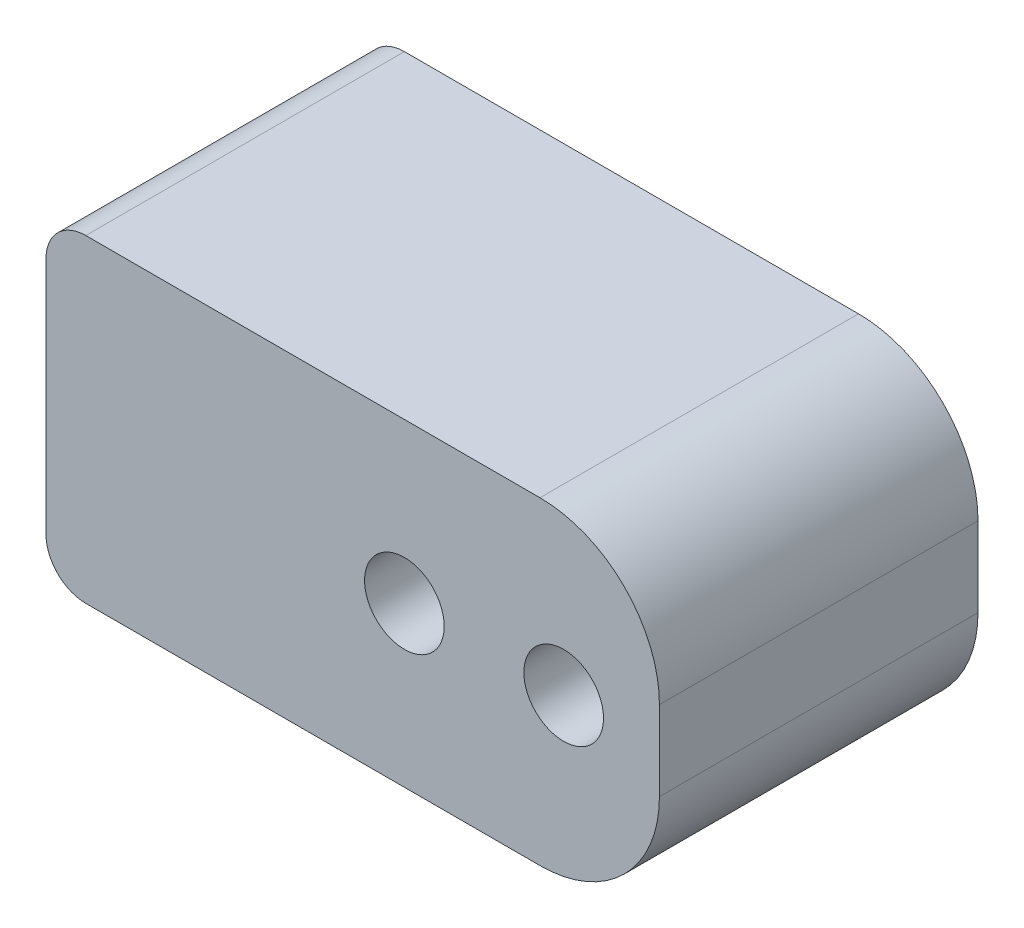
SolidWorks part; units mm, degrees
ref_plane "Front" through (0, 0, 0) normal (0, 0, 1) x (1, 0, 0)
ref_plane "Top" through (0, 0, 0) normal (0, 1, 0) x (1, 0, 0)
ref_plane "Right" through (0, 0, 0) normal (1, 0, 0) x (0, 0, -1)
sketch "Sketch1" plane through (0, 0, 0) normal (0, 0, 1) x (1, 0, 0)
  line L0 (-9, 4) -> (0, 4)
  line L1 (0, -4) -> (-9, -4)
  line L2 (-9, 4) -> (-9, -4)
  line L3 (55, 0) -> (-55, 0) construction
  line L4 (0, 4) -> (6.4045, 4)
  line L5 (0, 4) -> (0, -4)
  line L6 (0, -4) -> (6.4045, -4)
  line L7 (6.4045, 4) -> (6.4045, -4)
  circle A0 centre (0, 0) radius 4
  circle A1 centre (0, 0) radius 1
  circle A2 centre (4, 0) radius 1
  dimension "D1" = 8
  dimension "D3" = 2
  dimension "D4" = 4
  dimension "D2" = 9
extrude "Boss-Extrude1" add sketch "Sketch1" along normal blind 8 contours A0 L0 L2 L1 | A1 L5 A0 | A1 L5 A0 | A0 A2 L6 L7 L4 region at (-6.0028, 0, 0) region at (1.6632, 0, 0) region at (-1.7825, 0, 0) region at (3.2023, 3.8975, 0)
ref_plane "Plane1" through (0, 0, 4) normal (0, 0, 1) x (1, 0, 0)
sketch "Sketch3" plane through (0, 0, 4) normal (0, 0, 1) x (1, 0, 0)
  line L0 (4.4, 0) -> (-4.4, 0) construction
  circle A0 centre (-5, 0) radius 3.15
  circle A1 centre (0, 0) radius 1 construction
  dimension "D1" = 6.3
  dimension "D2" = 5
extrude "Cut-Extrude2" cut sketch "Sketch3" against normal mid plane 2.3
fillet "Fillet2" radius 1 2 edges at (-9, -4, 4) (-9, 4, 4)
fillet "Fillet3" radius 3 2 edges at (6.4045, -4, 4) (6.4045, 4, 4)
